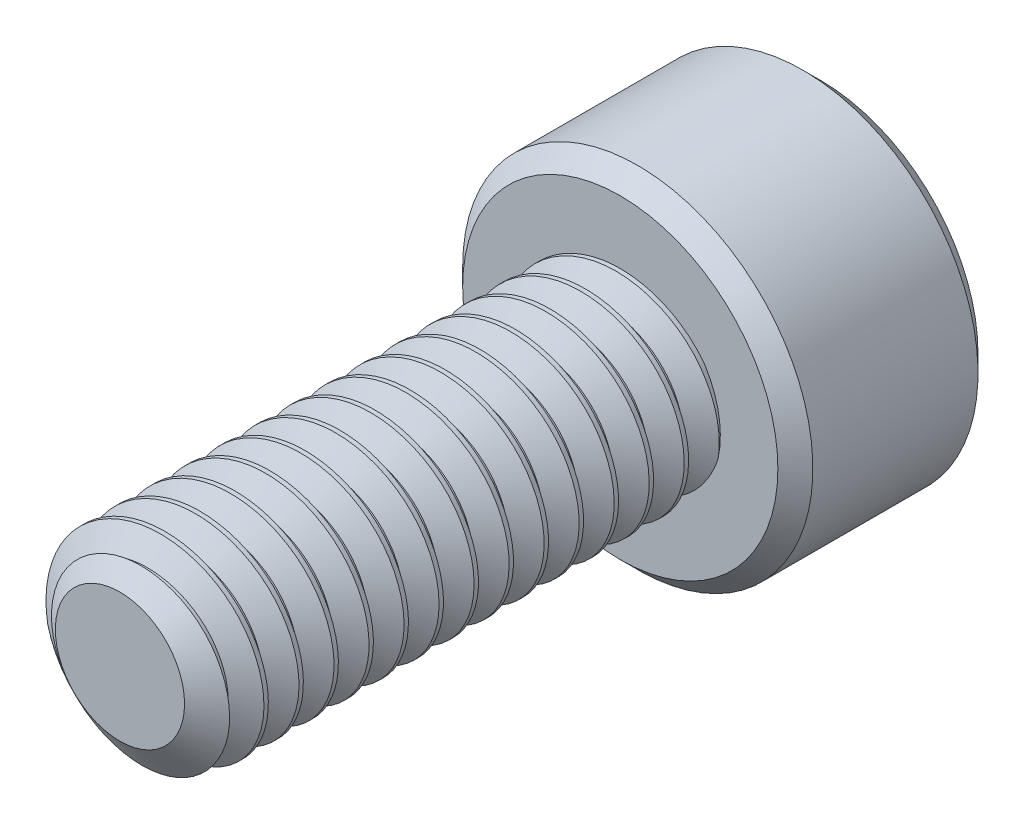
SolidWorks part; units mm, degrees
ref_plane "Front Plane" through (0, 0, 0) normal (0, 0, 1) x (1, 0, 0)
ref_plane "Top Plane" through (0, 0, 0) normal (0, 1, 0) x (1, 0, 0)
ref_plane "Right Plane" through (0, 0, 0) normal (1, 0, 0) x (0, 0, -1)
sketch "Sketch1" plane through (0, 0, 0) normal (0, 0, 1) x (1, 0, 0)
  circle A0 centre (0, 0) radius 2
  dimension "OD" = 4
extrude "Extrude1" add sketch "Sketch1" against normal blind 10
sketch "Sketch2" plane through (0, 0, 0) normal (0, 0, 1) x (1, 0, 0)
  circle A0 centre (0, 0) radius 2 construction
  circle A1 centre (0, 0) radius 2
curve "Helix/Spiral1" pitch 0.7 height 10.7 radius 2 centre (0, 0, 0) axis (0, 0, -1) start towards (0, 1, 0) parameters "pitch"=0.7
sketch "Sketch3" plane through (0, 0, 0) normal (1, 0, 0) x (0, 0, -1)
  line L0 (-0.6125, 2) -> (-0.35, 1.5453)
  line L1 (-0.35, 1.5453) -> (-0.2625, 1.5453)
  line L2 (-0.2625, 1.5453) -> (0, 2)
  line L3 (-0.6125, 2) -> (0, 2)
  line L4 (-0.3062, 2) -> (-0.3062, 1.5453) construction
  line L5 (-0.4812, 1.7727) -> (-0.1312, 1.7727) construction
  line L6 (0, 2) -> (0, -2) construction
  dimension "D1" = 0.0875
  dimension "D2" = 0.35
  dimension "D3" = 60
sweep "Cut-Sweep1" cut profiles "Sketch3" path "Helix/Spiral1" align with end faces yes
sketch "Sketch4" plane through (0, 0, 0) normal (1, 0, 0) x (0, 0, -1)
  line L0 (0.4962, 2) -> (0, 1.2913)
  line L1 (0, 1.2913) -> (0, 2)
  line L2 (0.4962, 2) -> (0, 2)
  line L3 (-0.6125, 2) -> (0, 2) construction
  line L4 (0, 0) -> (7.0209, 0) construction
  dimension "D1" = 55
  dimension "D2" = 0.254
revolve "Cut-Revolve1" cut sketch "Sketch4" angle 360 about L4
sketch "Sketch5" plane through (0, 0, 0) normal (1, 0, 0) x (0, 0, -1)
  line L0 (10, 0.3311) -> (10, 1.814) construction
  line L1 (10, 2.127) -> (1.2679, 2.127)
  line L2 (10, 2.127) -> (10, 0)
  line L3 (10, 0) -> (1, 0)
  line L4 (1, 1.127) -> (1, 0)
  line L5 (1.2679, 2.127) -> (1, 1.127)
  line L6 (0, 0) -> (1, 0) construction
  point P3 (1, 2.127)
  point P10 (1, 2.127)
  dimension "D1" = 1
  dimension "D2" = 0.127
  dimension "D3" = 15
  dimension "Thread Min" = 1
revolve "partially thread" [suppressed] add sketch "Sketch5" angle 360 about L6
sketch "Sketch6" plane through (0, 0, -10) normal (0, 0, -1) x (-1, 0, 0)
  circle A0 centre (0, 0) radius 3.5
  dimension "head dia" = 7
extrude "Extrude2" add sketch "Sketch6" along normal blind 4
sketch "Sketch7" plane through (0, 0, -14) normal (0, 0, -1) x (-1, 0, 0)
  line L1 (0, 1.7321) -> (-1.5, 0.866)
  line L2 (-1.5, 0.866) -> (-1.5, -0.866)
  line L3 (-1.5, -0.866) -> (0, -1.7321)
  line L4 (0, -1.7321) -> (1.5, -0.866)
  line L5 (1.5, -0.866) -> (1.5, 0.866)
  line L6 (1.5, 0.866) -> (0, 1.7321)
  circle A0 centre (0, 0) radius 1.5 construction
  dimension "hex dia" = 3
extrude "Cut-Extrude1" cut sketch "Sketch7" against normal blind 2.25
sketch "Sketch8" plane through (0, 0, -14) normal (0, 0, -1) x (-1, 0, 0)
  circle A0 centre (0, 0) radius 1.7321
extrude "Cut-Extrude2" cut sketch "Sketch8" against normal through all draft 45
chamfer "Chamfer1" distance 0.35 angle 45 2 edges at (-3.5, 0, -14) (-3.5, 0, -10)
sketch "Sketch9" plane through (0, 0, 0) normal (1, 0, 0) x (0, 0, -1)
  line L0 (0, 2) -> (0, -2) construction
  line L1 (3.85, 2) -> (3.85, -2) construction
  dimension "D1" = 3.85
equation "\"D3@Helix/Spiral1\" = \"screw length@Extrude1\"+\"pitch@Helix/Spiral1\""
equation "\"D1@Sketch3\" = \"pitch@Helix/Spiral1\"*.125"
equation "\"D2@Sketch3\" = \"pitch@Helix/Spiral1\"*.5"
equation "\"D1@Cut-Extrude1\" = \"hex dia@Sketch7\"*.75"
equation "\"D1@Chamfer1\" = \"head dia@Sketch6\"*.05"
equation "\"D1@Sketch9\" = \"pitch@Helix/Spiral1\"*5.5"
